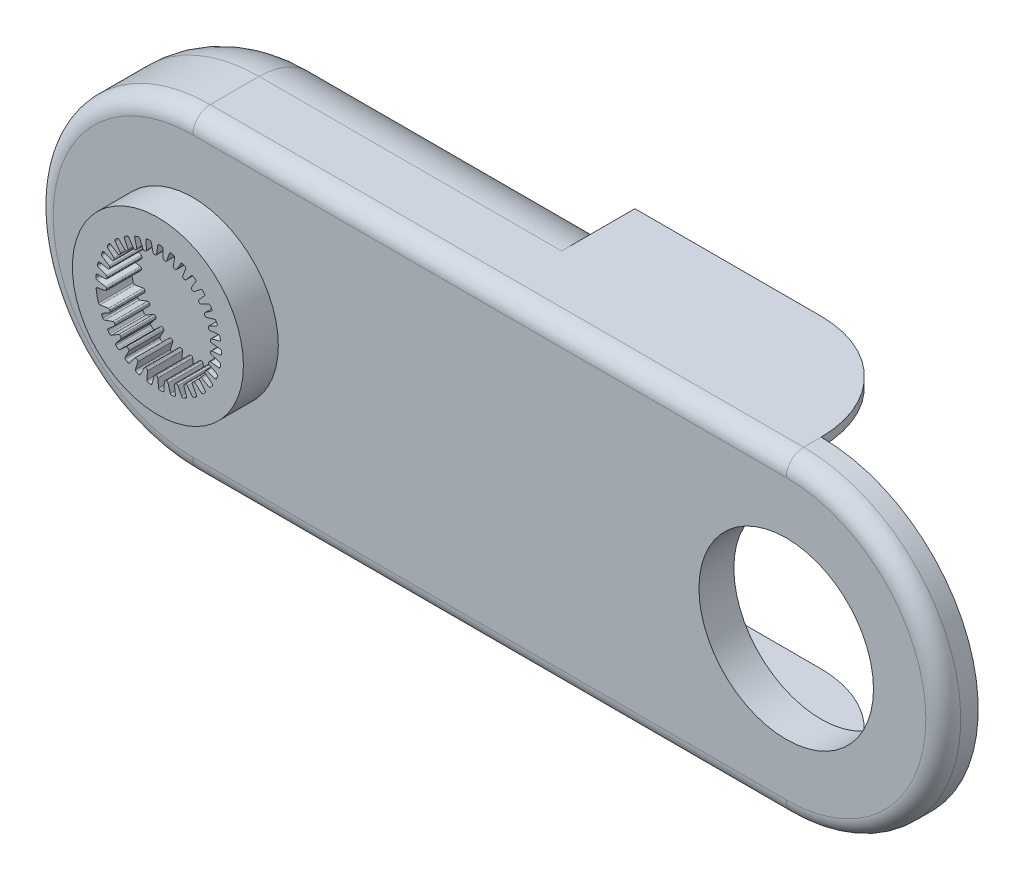
SolidWorks part; units mm, degrees
ref_plane "Front Plane" through (0, 0, 0) normal (0, 0, 1) x (1, 0, 0)
ref_plane "Top Plane" through (0, 0, 0) normal (0, 1, 0) x (1, 0, 0)
ref_plane "Right Plane" through (0, 0, 0) normal (1, 0, 0) x (0, 0, -1)
sketch "Sketch1" plane through (0, 0, 0) normal (0, 0, 1) x (1, 0, 0)
  line L0 (55, 0) -> (-55, 0) construction
  line L1 (-16.9691, -5.4979) -> (-14.565, -5.1246)
  line L2 (-14.1254, -5.3896) -> (-14.0498, -5.609)
  line L3 (-14.2318, -6.0878) -> (-16.2781, -7.2403)
  line L4 (-15.6283, -8.6059) -> (-13.3395, -7.7807)
  line L5 (-12.8575, -7.957) -> (-12.7414, -8.158)
  line L6 (-12.8287, -8.6627) -> (-14.6175, -10.1845)
  line L7 (-13.7191, -11.401) -> (-11.6298, -10.1543)
  line L8 (-11.1229, -10.2354) -> (-10.9707, -10.4105)
  line L9 (-10.96, -10.9225) -> (-12.4256, -12.7577)
  line L10 (-11.3116, -13.7804) -> (-9.4986, -12.158)
  line L11 (-8.9856, -12.1408) -> (-8.8027, -12.2837)
  line L12 (-8.6945, -12.7843) -> (-9.783, -14.8654)
  line L13 (-8.4943, -15.6568) -> (-7.0242, -13.7182)
  line L14 (-6.5239, -13.6035) -> (-6.3171, -13.7088)
  line L15 (-6.1154, -14.1796) -> (-6.7868, -16.4302)
  line L16 (-5.3708, -16.9611) -> (-4.2976, -14.7776)
  line L17 (-3.8283, -14.5696) -> (-3.6053, -14.6335)
  line L18 (-3.3174, -15.0571) -> (-3.5471, -17.3945)
  line L19 (-2.0557, -17.6455) -> (-1.4189, -15.2973)
  line L20 (-0.998, -15.0035) -> (-0.7668, -15.0238)
  line L21 (-0.4034, -15.3847) -> (-0.1828, -17.7229)
  line L22 (1.329, -17.6847) -> (1.5061, -15.2582)
  line L23 (1.8632, -14.8895) -> (2.094, -14.8652)
  line L24 (2.5196, -15.1502) -> (3.1822, -17.4034)
  line L25 (4.659, -17.0774) -> (4.3698, -14.6617)
  line L26 (4.65, -14.2316) -> (4.872, -14.1637)
  line L27 (5.3441, -14.3623) -> (6.4245, -16.4476)
  line L28 (7.8119, -15.8458) -> (7.0671, -13.5297)
  line L29 (7.2601, -13.054) -> (7.465, -12.9451)
  line L30 (7.9664, -13.0499) -> (9.4248, -14.8908)
  line L31 (10.6719, -14.0353) -> (9.4989, -11.9038)
  line L32 (9.5976, -11.4001) -> (9.7779, -11.254)
  line L33 (10.29, -11.2612) -> (12.073, -12.79)
  line L34 (13.1339, -11.7123) -> (11.5757, -9.8438)
  line L35 (11.5765, -9.3305) -> (11.7257, -9.1527)
  line L36 (12.2298, -9.0621) -> (14.2716, -10.2226)
  line L37 (15.1075, -8.9622) -> (13.2214, -7.4254)
  line L38 (13.1242, -6.9214) -> (13.2367, -6.7184)
  line L39 (13.7142, -6.5332) -> (15.94, -7.2828)
  line L40 (16.52, -5.8861) -> (14.3753, -4.7374)
  line L41 (14.1837, -4.2612) -> (14.2555, -4.0405)
  line L42 (14.6889, -3.7676) -> (17.0168, -4.0787)
  line L43 (17.3196, -2.597) -> (14.9951, -1.8786)
  line L44 (14.7162, -1.4477) -> (14.7445, -1.2173)
  line L45 (15.1179, -0.8668) -> (17.4624, -0.728)
  line L46 (17.477, 0.7843) -> (15.0581, 1.0459)
  line L47 (14.7021, 1.4157) -> (14.6859, 1.6472)
  line L48 (14.9856, 2.0626) -> (17.2605, 2.6462)
  line L49 (16.9862, 4.1334) -> (14.5619, 3.9288)
  line L50 (14.1419, 4.2238) -> (14.0818, 4.448)
  line L51 (14.2967, 4.9129) -> (16.4185, 5.9199)
  line L52 (15.8655, 7.3274) -> (13.5247, 6.6639)
  line L53 (13.0561, 6.8734) -> (12.9544, 7.082)
  line L54 (13.0766, 7.5794) -> (14.9673, 8.9727)
  line L55 (14.1559, 10.2489) -> (11.9847, 9.151)
  line L56 (11.4848, 9.2672) -> (11.3451, 9.4525)
  line L57 (11.3702, 9.9641) -> (12.9602, 11.6926)
  line L58 (11.9202, 12.7905) -> (9.9985, 11.2984)
  line L59 (9.4855, 11.3171) -> (9.3131, 11.4724)
  line L60 (9.2401, 11.9793) -> (10.4711, 13.9795)
  line L61 (9.2407, 14.8588) -> (7.6389, 13.0275)
  line L62 (7.1318, 12.9479) -> (6.9329, 13.0675)
  line L63 (6.7645, 13.5511) -> (7.5913, 15.7494)
  line L64 (6.2158, 16.3778) -> (4.9929, 14.2745)
  line L65 (4.5102, 14.0997) -> (4.2922, 14.1791)
  line L66 (4.0346, 14.6217) -> (4.4267, 16.9374)
  line L67 (2.9565, 17.2917) -> (2.1574, 14.9937)
  line L68 (1.7171, 14.73) -> (1.4878, 14.7663)
  line L69 (1.1505, 15.1517) -> (1.0936, 17.4997)
  line L70 (-0.4172, 17.567) -> (-0.7631, 15.1587)
  line L71 (-1.1451, 14.8159) -> (-1.377, 14.8078)
  line L72 (-1.7817, 15.1217) -> (-2.2855, 17.4156)
  line L73 (-3.7814, 17.1934) -> (-3.6615, 14.7634)
  line L74 (-3.971, 14.354) -> (-4.1972, 14.3018)
  line L75 (-4.6543, 14.5327) -> (-5.5866, 16.6884)
  line L76 (-7.0126, 16.1848) -> (-6.4312, 13.8224)
  line L77 (-6.6569, 13.3614) -> (-6.8689, 13.267)
  line L78 (-7.3617, 13.4065) -> (-8.6882, 15.3446)
  line L79 (-9.992, 14.5782) -> (-8.9705, 12.3701)
  line L80 (-9.1041, 11.8745) -> (-9.2942, 11.7414)
  line L81 (-9.8045, 11.7843) -> (-11.4765, 13.4337)
  line L82 (-12.61, 12.4326) -> (-11.1859, 10.46)
  line L83 (-11.2225, 9.948) -> (-11.3837, 9.7811)
  line L84 (-11.8929, 9.7258) -> (-13.8489, 11.0259)
  line L85 (-14.7706, 9.8269) -> (-12.9963, 8.1622)
  line L86 (-12.9345, 7.6527) -> (-13.0609, 7.458)
  line L87 (-13.5501, 7.3066) -> (-15.7182, 8.2096)
  line L88 (-16.3942, 6.8568) -> (-14.3349, 5.5613)
  line L89 (-14.177, 5.0729) -> (-14.264, 4.8577)
  line L90 (-14.7153, 4.6157) -> (-17.0159, 5.0884)
  line L91 (-17.4214, 3.6315) -> (-15.1526, 2.7527)
  line L92 (-14.9045, 2.3034) -> (-14.9488, 2.0756)
  line L93 (-15.3457, 1.7519) -> (-17.6942, 1.777)
  line L94 (-17.8142, 0.2694) -> (-15.4195, -0.1603)
  line L95 (-15.0901, -0.554) -> (-15.0901, -0.7861)
  line L96 (-15.418, -1.1795) -> (-17.7281, -1.6031)
  circle A0 centre (-0.372, 0) radius 24.5
  arc A1 (-18.0536, -2.0399) -> (-17.4139, -5.2165) centre (-0.1596, -0.0893) ccw
  arc A2 (-17.4139, -5.2165) -> (-16.9691, -5.4979) centre (-17.0305, -5.1026) ccw
  arc A3 (-14.1254, -5.3896) -> (-14.565, -5.1246) centre (-14.5036, -5.5198) ccw
  arc A4 (-14.2318, -6.0878) -> (-14.0498, -5.609) centre (-14.4281, -5.7393) ccw
  arc A5 (-16.2781, -7.2403) -> (-16.4437, -7.7593) centre (-16.0818, -7.5889) ccw
  arc A6 (-16.4437, -7.7593) -> (-16.1186, -8.4146) centre (-0.1596, -0.0893) ccw
  arc A7 (-16.1186, -8.4146) -> (-15.6283, -8.6059) centre (-15.764, -8.2296) ccw
  arc A8 (-12.8575, -7.957) -> (-13.3395, -7.7807) centre (-13.2039, -8.157) ccw
  arc A9 (-12.8287, -8.6627) -> (-12.7414, -8.158) centre (-13.0878, -8.358) ccw
  arc A10 (-14.6175, -10.1845) -> (-14.681, -10.7255) centre (-14.3583, -10.4892) ccw
  arc A11 (-14.681, -10.7255) -> (-14.2369, -11.3068) centre (-0.1596, -0.0893) ccw
  arc A12 (-14.2369, -11.3068) -> (-13.7191, -11.401) centre (-13.924, -11.0575) ccw
  arc A13 (-11.1229, -10.2354) -> (-11.6298, -10.1543) centre (-11.4248, -10.4978) ccw
  arc A14 (-10.96, -10.9225) -> (-10.9707, -10.4105) centre (-11.2726, -10.6729) ccw
  arc A15 (-12.4256, -12.7577) -> (-12.3847, -13.3009) centre (-12.1131, -13.0073) ccw
  arc A16 (-12.3847, -13.3009) -> (-11.8378, -13.7868) centre (-0.1596, -0.0893) ccw
  arc A17 (-11.8378, -13.7868) -> (-11.3116, -13.7804) centre (-11.5783, -13.4824) ccw
  arc A18 (-8.9856, -12.1408) -> (-9.4986, -12.158) centre (-9.2318, -12.456) ccw
  arc A19 (-8.6945, -12.7843) -> (-8.8027, -12.2837) centre (-9.049, -12.5989) ccw
  arc A20 (-9.783, -14.8654) -> (-9.6392, -15.3909) centre (-9.4286, -15.0508) ccw
  arc A21 (-9.6392, -15.3909) -> (-9.0097, -15.7634) centre (-0.1596, -0.0893) ccw
  arc A22 (-9.0097, -15.7634) -> (-8.4943, -15.6568) centre (-8.813, -15.4151) ccw
  arc A23 (-6.5239, -13.6035) -> (-7.0242, -13.7182) centre (-6.7055, -13.9599) ccw
  arc A24 (-6.1154, -14.1796) -> (-6.3171, -13.7088) centre (-6.4987, -14.0653) ccw
  arc A25 (-6.7868, -16.4302) -> (-6.5454, -16.9185) centre (-6.4035, -16.5446) ccw
  arc A26 (-6.5454, -16.9185) -> (-5.8563, -17.1641) centre (-0.1596, -0.0893) ccw
  arc A27 (-5.8563, -17.1641) -> (-5.3708, -16.9611) centre (-5.7297, -16.7847) ccw
  arc A28 (-3.8283, -14.5696) -> (-4.2976, -14.7776) centre (-3.9386, -14.9541) ccw
  arc A29 (-3.3174, -15.0571) -> (-3.6053, -14.6335) centre (-3.7155, -15.018) ccw
  arc A30 (-3.5471, -17.3945) -> (-3.2169, -17.8278) centre (-3.149, -17.4336) ccw
  arc A31 (-3.2169, -17.8278) -> (-2.4937, -17.9374) centre (-0.1596, -0.0893) ccw
  arc A32 (-2.4937, -17.9374) -> (-2.0557, -17.6455) centre (-2.4418, -17.5408) ccw
  arc A33 (-0.998, -15.0035) -> (-1.4189, -15.2973) centre (-1.0328, -15.402) ccw
  arc A34 (-0.4034, -15.3847) -> (-0.7668, -15.0238) centre (-0.8016, -15.4222) ccw
  arc A35 (-0.1828, -17.7229) -> (0.2239, -18.0853) centre (0.2154, -17.6853) ccw
  arc A36 (0.2239, -18.0853) -> (0.9548, -18.0548) centre (-0.1596, -0.0893) ccw
  arc A37 (0.9548, -18.0548) -> (1.329, -17.6847) centre (0.93, -17.6556) ccw
  arc A38 (1.8632, -14.8895) -> (1.5061, -15.2582) centre (1.905, -15.2873) ccw
  arc A39 (2.5196, -15.1502) -> (2.094, -14.8652) centre (2.1358, -15.263) ccw
  arc A40 (3.1822, -17.4034) -> (3.6506, -17.6814) centre (3.566, -17.2905) ccw
  arc A41 (3.6506, -17.6814) -> (4.3623, -17.5121) centre (-0.1596, -0.0893) ccw
  arc A42 (4.3623, -17.5121) -> (4.659, -17.0774) centre (4.2618, -17.1249) ccw
  arc A43 (4.65, -14.2316) -> (4.3698, -14.6617) centre (4.767, -14.6141) ccw
  arc A44 (5.3441, -14.3623) -> (4.872, -14.1637) centre (4.9889, -14.5463) ccw
  arc A45 (6.4245, -16.4476) -> (6.9374, -16.6312) centre (6.7797, -16.2636) ccw
  arc A46 (6.9374, -16.6312) -> (7.6036, -16.3292) centre (-0.1596, -0.0893) ccw
  arc A47 (7.6036, -16.3292) -> (7.8119, -15.8458) centre (7.4311, -15.9683) ccw
  arc A48 (7.2601, -13.054) -> (7.0671, -13.5297) centre (7.4479, -13.4072) ccw
  arc A49 (7.9664, -13.0499) -> (7.465, -12.9451) centre (7.6528, -13.2983) ccw
  arc A50 (9.4248, -14.8908) -> (9.9633, -14.9731) centre (9.7384, -14.6424) ccw
  arc A51 (9.9633, -14.9731) -> (10.5597, -14.5495) centre (-0.1596, -0.0893) ccw
  arc A52 (10.5597, -14.5495) -> (10.6719, -14.0353) centre (10.3215, -14.2282) ccw
  arc A53 (9.5976, -11.4001) -> (9.4989, -11.9038) centre (9.8493, -11.7109) ccw
  arc A54 (10.29, -11.2612) -> (9.7779, -11.254) centre (10.0297, -11.5649) ccw
  arc A55 (12.073, -12.79) -> (12.6173, -12.7681) centre (12.3334, -12.4864) ccw
  arc A56 (12.6173, -12.7681) -> (13.1219, -12.2385) centre (-0.1596, -0.0893) ccw
  arc A57 (13.1219, -12.2385) -> (13.1339, -11.7123) centre (12.8267, -11.9685) ccw
  arc A58 (11.5765, -9.3305) -> (11.5757, -9.8438) centre (11.8829, -9.5876) ccw
  arc A59 (12.2298, -9.0621) -> (11.7257, -9.1527) centre (12.0321, -9.4099) ccw
  arc A60 (14.2716, -10.2226) -> (14.8018, -10.0972) centre (14.4693, -9.8748) ccw
  arc A61 (14.8018, -10.0972) -> (15.196, -9.481) centre (-0.1596, -0.0893) ccw
  arc A62 (15.196, -9.481) -> (15.1075, -8.9622) centre (14.8548, -9.2723) ccw
  arc A63 (13.1242, -6.9214) -> (13.2214, -7.4254) centre (13.474, -7.1153) ccw
  arc A64 (13.7142, -6.5332) -> (13.2367, -6.7184) centre (13.5866, -6.9123) ccw
  arc A65 (15.94, -7.2828) -> (16.4365, -7.0586) centre (16.0677, -6.9037) ccw
  arc A66 (16.4365, -7.0586) -> (16.7059, -6.3785) centre (-0.1596, -0.0893) ccw
  arc A67 (16.7059, -6.3785) -> (16.52, -5.8861) centre (16.3311, -6.2387) ccw
  arc A68 (14.1837, -4.2612) -> (14.3753, -4.7374) centre (14.5642, -4.3848) ccw
  arc A69 (14.6889, -3.7676) -> (14.2555, -4.0405) centre (14.6359, -4.1641) ccw
  arc A70 (17.0168, -4.0787) -> (17.4613, -3.7638) centre (17.0698, -3.6822) ccw
  arc A71 (17.4613, -3.7638) -> (17.5961, -3.0448) centre (-0.1596, -0.0893) ccw
  arc A72 (17.5961, -3.0448) -> (17.3196, -2.597) centre (17.2015, -2.9792) ccw
  arc A73 (14.7162, -1.4477) -> (14.9951, -1.8786) centre (15.1133, -1.4964) ccw
  arc A74 (15.1179, -0.8668) -> (14.7445, -1.2173) centre (15.1415, -1.2661) ccw
  arc A75 (17.4624, -0.728) -> (17.8387, -0.3341) centre (17.4388, -0.3287) ccw
  arc A76 (17.8387, -0.3341) -> (17.8338, 0.3974) centre (-0.1596, -0.0893) ccw
  arc A77 (17.8338, 0.3974) -> (17.477, 0.7843) centre (17.434, 0.3866) ccw
  arc A78 (14.7021, 1.4157) -> (15.0581, 1.0459) centre (15.1011, 1.4436) ccw
  arc A79 (14.9856, 2.0626) -> (14.6859, 1.6472) centre (15.085, 1.6751) ccw
  arc A80 (17.2605, 2.6462) -> (17.5547, 3.1046) centre (17.1611, 3.0337) ccw
  arc A81 (17.5547, 3.1046) -> (17.4103, 3.8218) centre (-0.1596, -0.0893) ccw
  arc A82 (17.4103, 3.8218) -> (16.9862, 4.1334) centre (17.0199, 3.7348) ccw
  arc A83 (14.1419, 4.2238) -> (14.5619, 3.9288) centre (14.5283, 4.3274) ccw
  arc A84 (14.2967, 4.9129) -> (14.0818, 4.448) centre (14.4682, 4.5515) ccw
  arc A85 (16.4185, 5.9199) -> (16.6198, 6.426) centre (16.247, 6.2812) ccw
  arc A86 (16.6198, 6.426) -> (16.3413, 7.1024) centre (-0.1596, -0.0893) ccw
  arc A87 (16.3413, 7.1024) -> (15.8655, 7.3274) centre (15.9746, 6.9426) ccw
  arc A88 (13.0561, 6.8734) -> (13.5247, 6.6639) centre (13.4156, 7.0488) ccw
  arc A89 (13.0766, 7.5794) -> (12.9544, 7.082) centre (13.3139, 7.2574) ccw
  arc A90 (14.9673, 8.9727) -> (15.0684, 9.508) centre (14.73, 9.2947) ccw
  arc A91 (15.0684, 9.508) -> (14.6658, 10.1188) centre (-0.1596, -0.0893) ccw
  arc A92 (14.6658, 10.1188) -> (14.1559, 10.2489) centre (14.3364, 9.8919) ccw
  arc A93 (11.4848, 9.2672) -> (11.9847, 9.151) centre (11.8042, 9.5079) ccw
  arc A94 (11.3702, 9.9641) -> (11.3451, 9.4525) centre (11.6646, 9.6932) ccw
  arc A95 (12.9602, 11.6926) -> (12.9573, 12.2373) centre (12.6658, 11.9634) ccw
  arc A96 (12.9573, 12.2373) -> (12.4456, 12.7601) centre (-0.1596, -0.0893) ccw
  arc A97 (12.4456, 12.7601) -> (11.9202, 12.7905) centre (12.1655, 12.4745) ccw
  arc A98 (9.4855, 11.3171) -> (9.9985, 11.2984) centre (9.7532, 11.6144) ccw
  arc A99 (9.2401, 11.9793) -> (9.3131, 11.4724) centre (9.5807, 11.7697) ccw
  arc A100 (10.4711, 13.9795) -> (10.3643, 14.5136) centre (10.1304, 14.1891) ccw
  arc A101 (10.3643, 14.5136) -> (9.7623, 14.9292) centre (-0.1596, -0.0893) ccw
  arc A102 (9.7623, 14.9292) -> (9.2407, 14.8588) centre (9.5418, 14.5954) ccw
  arc A103 (7.1318, 12.9479) -> (7.6389, 13.0275) centre (7.3379, 13.2908) ccw
  arc A104 (6.7645, 13.5511) -> (6.9329, 13.0675) centre (7.1389, 13.4103) ccw
  arc A105 (7.5913, 15.7494) -> (7.3846, 16.2534) centre (7.2169, 15.8902) ccw
  arc A106 (7.3846, 16.2534) -> (6.7143, 16.5464) centre (-0.1596, -0.0893) ccw
  arc A107 (6.7143, 16.5464) -> (6.2158, 16.3778) centre (6.5616, 16.1768) ccw
  arc A108 (4.5102, 14.0997) -> (4.9929, 14.2745) centre (4.6471, 14.4756) ccw
  arc A109 (4.0346, 14.6217) -> (4.2922, 14.1791) centre (4.429, 14.5549) ccw
  arc A110 (4.4267, 16.9374) -> (4.1276, 17.3926) centre (4.0323, 17.0042) ccw
  arc A111 (4.1276, 17.3926) -> (3.4138, 17.5524) centre (-0.1596, -0.0893) ccw
  arc A112 (3.4138, 17.5524) -> (2.9565, 17.2917) centre (3.3343, 17.1604) ccw
  arc A113 (1.7171, 14.73) -> (2.1574, 14.9937) centre (1.7796, 15.1251) ccw
  arc A114 (1.1505, 15.1517) -> (1.4878, 14.7663) centre (1.5504, 15.1614) ccw
  arc A115 (1.0936, 17.4997) -> (0.7131, 17.8895) centre (0.6937, 17.49) ccw
  arc A116 (0.7131, 17.8895) -> (-0.0181, 17.9101) centre (-0.1596, -0.0893) ccw
  arc A117 (-0.0181, 17.9101) -> (-0.4172, 17.567) centre (-0.0212, 17.5101) ccw
  arc A118 (-1.1451, 14.8159) -> (-0.7631, 15.1587) centre (-1.1591, 15.2156) ccw
  arc A119 (-1.7817, 15.1217) -> (-1.377, 14.8078) centre (-1.391, 15.2075) ccw
  arc A120 (-2.2855, 17.4156) -> (-2.7334, 17.7257) centre (-2.6762, 17.3298) ccw
  arc A121 (-2.7334, 17.7257) -> (-3.4552, 17.6064) centre (-0.1596, -0.0893) ccw
  arc A122 (-3.4552, 17.6064) -> (-3.7814, 17.1934) centre (-3.3819, 17.2132) ccw
  arc A123 (-3.971, 14.354) -> (-3.6615, 14.7634) centre (-4.061, 14.7437) ccw
  arc A124 (-4.6543, 14.5327) -> (-4.1972, 14.3018) centre (-4.2871, 14.6915) ccw
  arc A125 (-5.5866, 16.6884) -> (-6.0854, 16.9073) centre (-5.9537, 16.5296) ccw
  arc A126 (-6.0854, 16.9073) -> (-6.7711, 16.6525) centre (-0.1596, -0.0893) ccw
  arc A127 (-6.7711, 16.6525) -> (-7.0126, 16.1848) centre (-6.6242, 16.2804) ccw
  arc A128 (-6.6569, 13.3614) -> (-6.4312, 13.8224) centre (-6.8196, 13.7268) ccw
  arc A129 (-7.3617, 13.4065) -> (-6.8689, 13.267) centre (-7.0316, 13.6324) ccw
  arc A130 (-8.6882, 15.3446) -> (-9.2196, 15.4643) centre (-9.0183, 15.1187) ccw
  arc A131 (-9.2196, 15.4643) -> (-9.8441, 15.0833) centre (-0.1596, -0.0893) ccw
  arc A132 (-9.8441, 15.0833) -> (-9.992, 14.5782) centre (-9.6289, 14.7462) ccw
  arc A133 (-9.1041, 11.8745) -> (-8.9705, 12.3701) centre (-9.3335, 12.2021) ccw
  arc A134 (-9.8045, 11.7843) -> (-9.2942, 11.7414) centre (-9.5236, 12.069) ccw
  arc A135 (-11.4765, 13.4337) -> (-12.021, 13.4498) centre (-11.7574, 13.1489) ccw
  arc A136 (-12.021, 13.4498) -> (-12.5613, 12.9567) centre (-0.1596, -0.0893) ccw
  arc A137 (-12.5613, 12.9567) -> (-12.61, 12.4326) centre (-12.2857, 12.6668) ccw
  arc A138 (-11.2225, 9.948) -> (-11.1859, 10.46) centre (-11.5103, 10.2259) ccw
  arc A139 (-11.8929, 9.7258) -> (-11.3837, 9.7811) centre (-11.6715, 10.0589) ccw
  arc A140 (-13.8489, 11.0259) -> (-14.3864, 10.9378) centre (-14.0703, 10.6928) ccw
  arc A141 (-14.3864, 10.9378) -> (-14.8227, 10.3506) centre (-0.1596, -0.0893) ccw
  arc A142 (-14.8227, 10.3506) -> (-14.7706, 9.8269) centre (-14.4969, 10.1186) ccw
  arc A143 (-12.9345, 7.6527) -> (-12.9963, 8.1622) centre (-13.27, 7.8705) ccw
  arc A144 (-13.5501, 7.3066) -> (-13.0609, 7.458) centre (-13.3963, 7.6759) ccw
  arc A145 (-15.7182, 8.2096) -> (-16.2291, 8.0206) centre (-15.872, 7.8404) ccw
  arc A146 (-16.2291, 8.0206) -> (-16.5454, 7.361) centre (-0.1596, -0.0893) ccw
  arc A147 (-16.5454, 7.361) -> (-16.3942, 6.8568) centre (-16.1812, 7.1954) ccw
  arc A148 (-14.177, 5.0729) -> (-14.3349, 5.5613) centre (-14.5479, 5.2227) ccw
  arc A149 (-14.7153, 4.6157) -> (-14.264, 4.8577) centre (-14.6348, 5.0075) ccw
  arc A150 (-17.0159, 5.0884) -> (-17.4813, 4.8054) centre (-17.0964, 4.6966) ccw
  arc A151 (-17.4813, 4.8054) -> (-17.6659, 4.0975) centre (-0.1596, -0.0893) ccw
  arc A152 (-17.6659, 4.0975) -> (-17.4214, 3.6315) centre (-17.2769, 4.0045) ccw
  arc A153 (-14.9045, 2.3034) -> (-15.1526, 2.7527) centre (-15.2971, 2.3797) ccw
  arc A154 (-15.3457, 1.7519) -> (-14.9488, 2.0756) centre (-15.3414, 2.1519) ccw
  arc A155 (-17.6942, 1.777) -> (-18.097, 1.4103) centre (-17.6984, 1.377) ccw
  arc A156 (-18.097, 1.4103) -> (-18.1432, 0.6803) centre (-0.1596, -0.0893) ccw
  arc A157 (-18.1432, 0.6803) -> (-17.8142, 0.2694) centre (-17.7435, 0.6632) ccw
  arc A158 (-15.0901, -0.554) -> (-15.4195, -0.1603) centre (-15.4901, -0.554) ccw
  arc A159 (-15.418, -1.1795) -> (-15.0901, -0.7861) centre (-15.4901, -0.7861) ccw
  arc A160 (-17.7281, -1.6031) -> (-18.0536, -2.0399) centre (-17.656, -1.9965) ccw
  point P4 (0, 0)
  dimension "D1" = 49
extrude "Boss-Extrude1" add sketch "Sketch1" along normal blind 10
sketch "Sketch6" plane through (0, 0, 0) normal (0, 0, 1) x (1, 0, 0)
  line L0 (-0.372, 0) -> (169.628, 0) construction
  line L1 (-0.372, 45) -> (169.628, 45)
  line L2 (169.628, -45) -> (-0.372, -45)
  arc A1 (169.628, -45) -> (169.628, 45) centre (169.628, 0) ccw
  arc A2 (-0.372, 45) -> (-0.372, -45) centre (-0.372, 0) ccw
  dimension "D1" = 170
  dimension "D2" = 90
extrude "Boss-Extrude3" add sketch "Sketch6" against normal blind 40
sketch "Sketch7" plane through (0, 0, -40) normal (0, 0, -1) x (-1, 0, 0)
  line L6 (-174.2492, 0) -> (0, 0) construction
  line L7 (-169.628, 42.5) -> (-91.4373, 42.5)
  line L8 (-257.0612, 42.5) -> (-257.0612, -42.5)
  line L9 (-169.628, -42.5) -> (-91.4373, -42.5)
  line L10 (-91.4373, 42.5) -> (-91.4373, -42.5)
  line L11 (-257.0612, 42.5) -> (-91.4373, -42.5) construction
  line L12 (-257.0612, -42.5) -> (-91.4373, 42.5) construction
  line L13 (-169.628, 45) -> (-169.628, 42.5)
  line L14 (-169.628, 45) -> (-257.0612, 45)
  line L15 (-257.0612, 45) -> (-257.0612, 42.5)
  line L16 (-169.628, -45) -> (-169.628, -42.5)
  line L17 (-169.628, -45) -> (-257.0612, -45)
  line L18 (-257.0612, -45) -> (-257.0612, -42.5)
  point P0 (-174.2492, 0)
  point P13 (0, 0)
  point P18 (0, 0)
  point P19 (0, 0)
  point P20 (0, 0)
  point P21 (0, 0)
  point P22 (0, 0)
  dimension "D1" = 85
extrude "Cut-Extrude3" cut sketch "Sketch7" against normal blind 30
fillet "Fillet12" radius 5 4 edges at (-45.372, 0, 0) (84.628, -45, 0) (84.628, 45, 0) (214.628, 0, 0)
fillet "Fillet14" radius 30 2 edges at (169.628, -43.75, -40) (169.628, 43.75, -40)
sketch "Sketch8" plane through (0, 0, -40) normal (0, 0, -1) x (-1, 0, 0)
  line L0 (-139.628, 45) -> (0.372, 45) construction
  line L1 (-86.2755, 45) -> (62.0003, 45)
  line L2 (-86.2755, 45) -> (-86.2755, -45)
  line L3 (-86.2755, -45) -> (62.0003, -45)
  line L4 (62.0003, 45) -> (62.0003, -45)
  line L5 (0.372, -45) -> (-139.628, -45) construction
extrude "Cut-Extrude4" cut sketch "Sketch8" against normal blind 1
fillet "Fillet16" radius 20 3 edges at (42.9518, -45, -39) (-45.372, 0, -39) (42.9518, 45, -39)
sketch "Sketch9" plane through (0, 0, -10) normal (0, 0, -1) x (-1, 0, 0)
  circle A0 centre (-169.628, 0) radius 25
extrude "Cut-Extrude5" cut sketch "Sketch9" against normal through all
